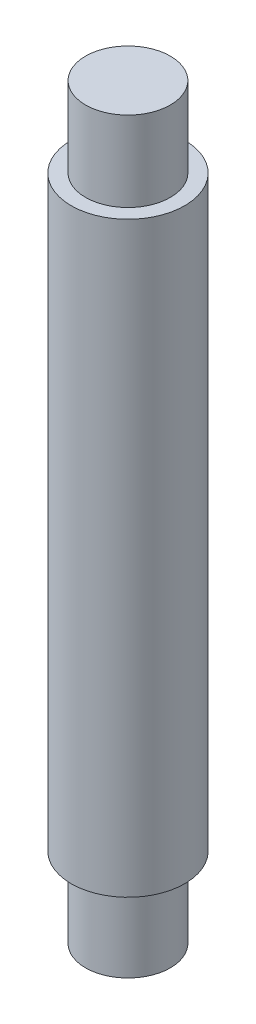
SolidWorks part; units mm, degrees
ref_plane "Plano frontal" through (0, 0, 0) normal (0, 0, 1) x (1, 0, 0)
ref_plane "Plano superior" through (0, 0, 0) normal (0, 1, 0) x (1, 0, 0)
ref_plane "Plano direito" through (0, 0, 0) normal (1, 0, 0) x (0, 0, -1)
sketch "Esboço1" plane through (0, 0, 0) normal (0, 1, 0) x (1, 0, 0)
  circle A0 centre (0, 0) radius 4.25
  circle A1 centre (0, 0) radius 3.175
  dimension "D1" = 8.5
  dimension "D2" = 6.35
extrude "Ressalto-extrusão1" add sketch "Esboço1" along normal blind 44 contours A0
sketch "Esboço2" plane through (0, 0, 0) normal (0, -1, 0) x (-1, 0, 0)
  circle A0 centre (0, 0) radius 3.175
  dimension "D1" = 6.35
extrude "Ressalto-extrusão2" add sketch "Esboço2" against normal blind 50 and the other way blind 6
